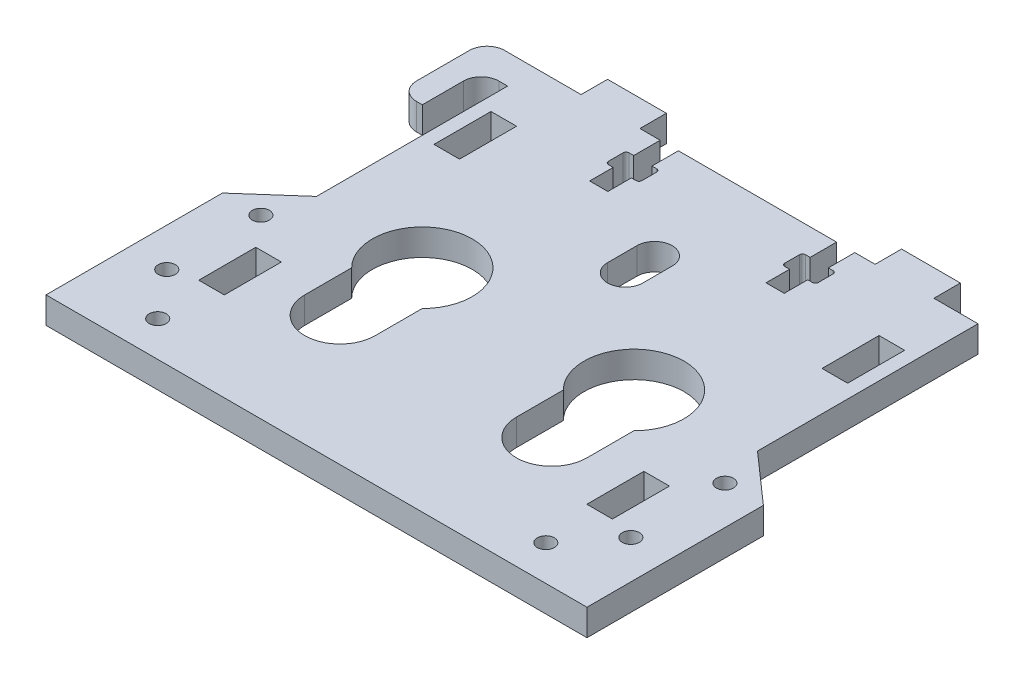
SolidWorks part; units mm, degrees
ref_plane "Front Plane" through (0, 0, 0) normal (0, 0, 1) x (1, 0, 0)
ref_plane "Top Plane" through (0, 0, 0) normal (0, 1, 0) x (1, 0, 0)
ref_plane "Right Plane" through (0, 0, 0) normal (1, 0, 0) x (0, 0, -1)
sketch "Sketch1" plane through (0, 0, 0) normal (0, 1, 0) x (1, 0, 0)
  line L1 (-37.5, 37.5) -> (37.5, 37.5)
  line L2 (-37.5, 37.5) -> (-37.5, -37.5)
  line L3 (-37.5, -37.5) -> (37.5, -37.5)
  line L4 (37.5, 37.5) -> (37.5, -37.5)
  line L5 (-37.5, 37.5) -> (37.5, -37.5) construction
  line L6 (-37.5, -37.5) -> (37.5, 37.5) construction
  point P0 (0, 0)
  dimension "D1" = 75
  dimension "D2" = 75
extrude "MainShape" add sketch "Sketch1" along normal blind 4.5
sketch "Sketch2" plane through (0, 4.5, 0) normal (0, 1, 0) x (1, 0, 0)
  line L0 (0, -37.5) -> (0, 37.5) construction
  line L1 (-37.5, -37.5) -> (37.5, -37.5) construction
  line L2 (37.5, 37.5) -> (-37.5, 37.5) construction
  line L4 (-5, 42) -> (5, 42)
  line L5 (-5, 42) -> (-5, 33)
  line L6 (-5, 33) -> (5, 33)
  line L7 (5, 42) -> (5, 33)
  line L8 (-5, 42) -> (5, 33) construction
  line L9 (-5, 33) -> (5, 42) construction
  dimension "D1" = 10
  dimension "D2" = 4.5
extrude "Tab1" [suppressed] add sketch "Sketch2" against normal through all
sketch "Sketch4" [suppressed] plane through (0, 4.5, 0) normal (0, 1, 0) x (1, 0, 0)
  line L0 (0, 42) -> (0, -37.5) construction
  line L1 (5, 42) -> (-5, 42) construction
  line L2 (-47.5, -37.5) -> (47.5, -37.5) construction
  line L3 (-40, 37.5) -> (-40, 27) construction
  line L4 (-5, 37.5) -> (-47.5, 37.5) construction
  line L5 (-38.25, 27) -> (-41.75, 27) construction
  line L6 (-41.75, 27) -> (-41.75, 37.5) construction
  line L7 (-38.25, 27) -> (-41.75, 27)
  line L8 (-41.75, 27) -> (-41.75, 29.5)
  line L9 (-41.75, 29.5) -> (-42.75, 29.5)
  line L10 (-43, 29.75) -> (-43, 33.45)
  line L11 (-42.75, 33.7) -> (-41.75, 33.7)
  line L12 (-41.75, 33.7) -> (-41.75, 37.5)
  line L13 (-41.75, 37.5) -> (-38.25, 37.5)
  line L14 (-38.25, 27) -> (-38.25, 37.5) construction
  line L15 (-38.25, 33.7) -> (-38.25, 37.5)
  line L16 (-37.25, 33.7) -> (-38.25, 33.7)
  line L17 (-37, 29.75) -> (-37, 33.45)
  line L18 (-38.25, 29.5) -> (-37.25, 29.5)
  line L19 (-38.25, 27) -> (-38.25, 29.5)
  line L20 (38.25, 27) -> (38.25, 37.5) construction
  line L21 (41.75, 27) -> (41.75, 37.5) construction
  line L22 (38.25, 27) -> (41.75, 27) construction
  line L23 (40, 37.5) -> (40, 27) construction
  line L24 (38.25, 27) -> (38.25, 29.5)
  line L25 (38.25, 29.5) -> (37.25, 29.5)
  line L26 (37, 29.75) -> (37, 33.45)
  line L27 (37.25, 33.7) -> (38.25, 33.7)
  line L28 (38.25, 33.7) -> (38.25, 37.5)
  line L29 (41.75, 37.5) -> (38.25, 37.5)
  line L30 (41.75, 33.7) -> (41.75, 37.5)
  line L31 (42.75, 33.7) -> (41.75, 33.7)
  line L32 (43, 29.75) -> (43, 33.45)
  line L33 (41.75, 29.5) -> (42.75, 29.5)
  line L34 (41.75, 27) -> (41.75, 29.5)
  line L35 (38.25, 27) -> (41.75, 27)
  arc A0 (-42.75, 29.5) -> (-43, 29.75) centre (-42.75, 29.75) cw
  arc A1 (-37, 29.75) -> (-37.25, 29.5) centre (-37.25, 29.75) cw
  arc A2 (-37.25, 33.7) -> (-37, 33.45) centre (-37.25, 33.45) cw
  arc A3 (-43, 33.45) -> (-42.75, 33.7) centre (-42.75, 33.45) cw
  arc A4 (43, 33.45) -> (42.75, 33.7) centre (42.75, 33.45) ccw
  arc A5 (37.25, 33.7) -> (37, 33.45) centre (37.25, 33.45) ccw
  arc A6 (37, 29.75) -> (37.25, 29.5) centre (37.25, 29.75) ccw
  arc A7 (42.75, 29.5) -> (43, 29.75) centre (42.75, 29.75) ccw
  point P24 (-43, 29.5)
  point P27 (-37, 29.5)
  point P30 (-37, 33.7)
  point P33 (-43, 33.7)
  point P56 (43, 33.7)
  point P57 (37, 33.7)
  point P58 (37, 29.5)
  point P59 (43, 29.5)
  dimension "D7" = 0.5
  dimension "D1" = 11
  dimension "D2" = 1.55
  dimension "D3" = 3.5
  dimension "D4" = 2.85
  dimension "D5" = 8
  dimension "D6" = 40
extrude "Cut-Extrude2" [suppressed] cut sketch "Sketch4" against normal through all
sketch "Sketch5" plane through (0, 4.5, 0) normal (0, 1, 0) x (1, 0, 0)
  line L0 (0, -37.5) -> (0, 37.5) construction
  line L1 (-37.5, -37.5) -> (37.5, -37.5) construction
  line L3 (33, 37.5) -> (33, -37.5) construction
  line L4 (37.5, 37.5) -> (-37.5, 37.5) construction
  line L5 (-33, 37.5) -> (-33, -37.5) construction
  line L6 (30.825, 27.35) -> (35.175, 27.35)
  line L7 (30.825, 27.35) -> (30.825, 17.65)
  line L8 (30.825, 17.65) -> (35.175, 17.65)
  line L9 (35.175, 27.35) -> (35.175, 17.65)
  line L10 (30.825, 27.35) -> (35.175, 17.65) construction
  line L11 (30.825, 17.65) -> (35.175, 27.35) construction
  line L12 (-30.825, 17.65) -> (-35.175, 27.35) construction
  line L13 (-30.825, 27.35) -> (-35.175, 17.65) construction
  line L14 (-35.175, 27.35) -> (-35.175, 17.65)
  line L15 (-30.825, 17.65) -> (-35.175, 17.65)
  line L16 (-30.825, 27.35) -> (-30.825, 17.65)
  line L17 (-30.825, 27.35) -> (-35.175, 27.35)
  line L18 (-37.5, 2.5) -> (37.5, 2.5) construction
  line L19 (-37.5, 37.5) -> (-37.5, -37.5) construction
  line L20 (37.5, -37.5) -> (37.5, 37.5) construction
  line L21 (-30.825, -22.35) -> (-35.175, -12.65) construction
  line L22 (-30.825, -12.65) -> (-35.175, -22.35) construction
  line L23 (30.825, -12.65) -> (35.175, -22.35) construction
  line L24 (30.825, -22.35) -> (35.175, -12.65) construction
  line L25 (-30.825, -22.35) -> (-35.175, -22.35)
  line L26 (-30.825, -22.35) -> (-30.825, -12.65)
  line L27 (-30.825, -12.65) -> (-35.175, -12.65)
  line L28 (-35.175, -22.35) -> (-35.175, -12.65)
  line L29 (35.175, -22.35) -> (35.175, -12.65)
  line L30 (30.825, -12.65) -> (35.175, -12.65)
  line L31 (30.825, -22.35) -> (30.825, -12.65)
  line L32 (30.825, -22.35) -> (35.175, -22.35)
  line L33 (-30.825, 27.35) -> (-35.175, 17.65) construction
  line L34 (-37.5, 37.5) -> (37.5, 37.5) construction
  line L35 (37.5, 37.5) -> (-37.5, 37.5) construction
  point P10 (33, 22.5)
  point P21 (-33, 22.5)
  point P36 (-33, -17.5)
  point P37 (33, -17.5)
  dimension "D1" = 33
  dimension "D2" = 9.7
  dimension "D3" = 4.35
  dimension "D4" = 15
  dimension "D5" = 40
extrude "Cut-Extrude3" cut sketch "Sketch5" against normal through all
sketch "Sketch6" plane through (0, 4.5, 0) normal (0, 1, 0) x (1, 0, 0)
  line L0 (-18, -37.5) -> (-18, 28) construction
  line L1 (-24, -15.5) -> (-24, -7.5208)
  line L3 (-37.5, -15.5) -> (37.5, -15.5) construction
  line L4 (-37.5, 37.5) -> (-37.5, -37.5) construction
  line L5 (37.5, -37.5) -> (37.5, 37.5) construction
  line L6 (37.5, 37.5) -> (-37.5, 37.5) construction
  line L7 (-37.5, -37.5) -> (37.5, -37.5) construction
  line L8 (-12, -15.5) -> (-12, -7.5208)
  line L9 (-37.5, 37.5) -> (37.5, 37.5) construction
  arc A0 (-24, -15.5) -> (-12, -15.5) centre (-18, -15.5) ccw
  arc A2 (-12, -7.5208) -> (-24, -7.5208) centre (-18, -1.5) ccw
  dimension "D1" = 12
  dimension "D6" = 8.5
  dimension "D2" = 53
  dimension "D3" = 0
  dimension "D5" = 0
  dimension "D7" = 14
  dimension "D4" = 18
extrude "Cut-Extrude4" cut sketch "Sketch6" against normal through all
sketch "Sketch13" plane through (0, 4.5, 0) normal (0, 1, 0) x (1, 0, 0)
  line L0 (-37.5, 0) -> (-46, -7.5)
  line L1 (-37.5, 37.5) -> (-37.5, -37.5) construction
  line L2 (-46, -7.5) -> (-46, -37.5)
  line L3 (-46, -37.5) -> (-37.5, -37.5)
  line L4 (-37.5, -37.5) -> (-37.5, 0)
  line L5 (0, 37.5) -> (0, -37.5) construction
  line L6 (37.5, 37.5) -> (-37.5, 37.5) construction
  line L7 (-37.5, -37.5) -> (37.5, -37.5) construction
  line L8 (37.5, -37.5) -> (37.5, 0)
  line L9 (46, -37.5) -> (37.5, -37.5)
  line L10 (46, -7.5) -> (46, -37.5)
  line L11 (37.5, 0) -> (46, -7.5)
  line L12 (-37.5, -37.5) -> (-37.5, 0)
  line M23 (37.5, -37.5) -> (37.5, 37.5)
  line M25 (-37.5, 37.5) -> (-37.5, -37.5)
  dimension "D1" = 46
  dimension "D2" = 30
extrude "Boss-Extrude2" add sketch "Sketch13" against normal through all contours L2 L3 L0 M25 | L11 L9 L10 M23 region at (-41.5926, 4.5, 20.5556) region at (41.5926, 4.5, 20.5556)
sketch "Sketch8" plane through (0, 4.5, 0) normal (0, 1, 0) x (1, 0, 0)
  line L0 (-18, -9.5) -> (-18, -21.5) construction
  line L1 (-18, -15.5) -> (-39.46, -15.5) construction
  line L2 (-39.46, -23.5) -> (-39.46, -7.5) construction
  line L3 (-18, -21.5) -> (-18, -9.5) construction
  circle A0 centre (-39.46, -7.5) radius 1.45
  circle A1 centre (-18, -15.5) radius 6 construction
  circle A2 centre (-39.46, -23.5) radius 1.45
  dimension "D3" = 2.9
  dimension "D1" = 0
  dimension "D2" = 8
  dimension "D4" = 21.46
extrude "Cut-Extrude6" cut sketch "Sketch8" against normal through all
mirror "Mirror1" about plane through (0, 0, 0) normal (1, 0, 0) of "Cut-Extrude6", "Cut-Extrude4"
sketch "Sketch11" plane through (0, 4.5, 0) normal (0, 1, 0) x (1, 0, 0)
  line L0 (0, 37.5) -> (0, -37.5) construction
  line L1 (37.5, 37.5) -> (-37.5, 37.5) construction
  line L2 (-46, -37.5) -> (46, -37.5) construction
  line L3 (-25, 42) -> (-25, 37.5) construction
  line L4 (-30, 37.5) -> (-20, 37.5)
  line L5 (-30, 37.5) -> (-30, 42)
  line L6 (-30, 42) -> (-20, 42)
  line L7 (-20, 37.5) -> (-20, 42)
  line L8 (25, 42) -> (25, 37.5) construction
  line L9 (20, 37.5) -> (20, 42)
  line L10 (30, 42) -> (20, 42)
  line L11 (30, 37.5) -> (30, 42)
  line L12 (30, 37.5) -> (20, 37.5)
  dimension "D1" = 10
  dimension "D2" = 4.5
  dimension "D3" = 25
extrude "RearTabs" add sketch "Sketch11" against normal through all
sketch "Sketch12" plane through (0, 4.5, 0) normal (0, 1, 0) x (1, 0, 0)
  line L0 (-15, 0) -> (-15, 37.5) construction
  line L1 (20, 37.5) -> (-20, 37.5) construction
  line L2 (-13.45, 37.5) -> (-16.55, 37.5)
  line L3 (-16.55, 37.5) -> (-16.55, 33)
  line L4 (-16.55, 33) -> (-17.35, 33)
  line L5 (-17.85, 32.5) -> (-17.85, 30)
  line L6 (-17.35, 29.5) -> (-16.55, 29.5)
  line L7 (-16.55, 29.5) -> (-16.55, 25.5)
  line L8 (-16.55, 25.5) -> (-13.45, 25.5)
  line L9 (-13.45, 29.5) -> (-13.45, 25.5)
  line L10 (-12.65, 29.5) -> (-13.45, 29.5)
  line L11 (-12.15, 32.5) -> (-12.15, 30)
  line L12 (-13.45, 33) -> (-12.65, 33)
  line L13 (-13.45, 37.5) -> (-13.45, 33)
  line L14 (0, 37.5) -> (0, 23.4067) construction
  line L15 (13.45, 37.5) -> (13.45, 33)
  line L16 (13.45, 33) -> (12.65, 33)
  line L17 (12.15, 32.5) -> (12.15, 30)
  line L18 (12.65, 29.5) -> (13.45, 29.5)
  line L19 (13.45, 29.5) -> (13.45, 25.5)
  line L20 (16.55, 25.5) -> (13.45, 25.5)
  line L21 (16.55, 29.5) -> (16.55, 25.5)
  line L22 (17.35, 29.5) -> (16.55, 29.5)
  line L23 (17.85, 32.5) -> (17.85, 30)
  line L24 (16.55, 33) -> (17.35, 33)
  line L25 (16.55, 37.5) -> (16.55, 33)
  line L26 (13.45, 37.5) -> (16.55, 37.5)
  arc A0 (-17.85, 30) -> (-17.35, 29.5) centre (-17.35, 30) ccw
  arc A1 (-17.35, 33) -> (-17.85, 32.5) centre (-17.35, 32.5) ccw
  arc A2 (-12.65, 33) -> (-12.15, 32.5) centre (-12.65, 32.5) cw
  arc A3 (-12.15, 30) -> (-12.65, 29.5) centre (-12.65, 30) cw
  arc A4 (12.15, 30) -> (12.65, 29.5) centre (12.65, 30) ccw
  arc A5 (12.65, 33) -> (12.15, 32.5) centre (12.65, 32.5) ccw
  arc A6 (17.35, 33) -> (17.85, 32.5) centre (17.35, 32.5) cw
  arc A7 (17.85, 30) -> (17.35, 29.5) centre (17.35, 30) cw
  point P14 (-17.85, 29.5)
  point P17 (-17.85, 33)
  point P25 (-15, 25.5)
  point P28 (-12.15, 33)
  point P29 (-12.15, 29.5)
  point P53 (12.15, 29.5)
  point P54 (12.15, 33)
  point P55 (15, 25.5)
  point P56 (17.85, 33)
  point P57 (17.85, 29.5)
  dimension "D5" = 8
  dimension "D1" = 12
  dimension "D6" = 0.5
  dimension "D2" = 3.5
  dimension "D3" = 2.85
  dimension "D4" = 1.55
  dimension "D7" = 15
extrude "FrontScrewSlot" cut sketch "Sketch12" against normal through all
sketch "Sketch14" plane through (0, 4.5, 0) normal (0, 1, 0) x (1, 0, 0)
  line L0 (-33, 27.35) -> (-33, -37.5) construction
  line L1 (-30.825, 27.35) -> (-35.175, 27.35) construction
  line L2 (-46, -37.5) -> (46, -37.5) construction
  line L3 (-30, 37.5) -> (-37.5, 37.5) construction
  line L4 (0, 0) -> (0, -37.5) construction
  line L5 (33, 27.35) -> (33, -37.5) construction
  line L6 (-33, 27.35) -> (-33, -37.5) construction
  circle A0 centre (-33, -31.5) radius 1.45
  circle A1 centre (33, -31.5) radius 1.45
  dimension "D2" = 2.9
  dimension "D1" = 69
extrude "BraceScrews" cut sketch "Sketch14" against normal through all
sketch "Sketch15" plane through (0, 4.5, 0) normal (0, 1, 0) x (1, 0, 0)
  line L0 (0, -37.5) -> (0, 25.5) construction
  line L1 (-46, -37.5) -> (46, -37.5) construction
  line L2 (-16.55, 25.5) -> (-13.45, 25.5) construction
  line L3 (16, 27.5) -> (-16, 27.5) construction
  line L4 (-16.55, 37.5) -> (-20, 37.5) construction
  line L5 (-18.175, 32.35) -> (-13.825, 32.35)
  line L6 (-18.175, 32.35) -> (-18.175, 22.65)
  line L7 (-18.175, 22.65) -> (-13.825, 22.65)
  line L8 (-13.825, 32.35) -> (-13.825, 22.65)
  line L9 (-18.175, 32.35) -> (-13.825, 22.65) construction
  line L10 (-18.175, 22.65) -> (-13.825, 32.35) construction
  line L11 (18.175, 22.65) -> (13.825, 32.35) construction
  line L12 (18.175, 32.35) -> (13.825, 22.65) construction
  line L13 (13.825, 32.35) -> (13.825, 22.65)
  line L14 (18.175, 22.65) -> (13.825, 22.65)
  line L15 (18.175, 32.35) -> (18.175, 22.65)
  line L16 (18.175, 32.35) -> (13.825, 32.35)
  point P19 (0, 27.5)
  dimension "D1" = 16
  dimension "D2" = 4.35
  dimension "D3" = 9.7
  dimension "D4" = 10
extrude "FanTabs" [suppressed] cut sketch "Sketch15" against normal through all
sketch "Sketch16" plane through (0, 4.5, 0) normal (0, 1, 0) x (1, 0, 0)
  line L0 (0, 0) -> (0, 37.5) construction
  line L2 (0, 20) -> (0, 15) construction
  line L3 (3, 20) -> (3, 15)
  line L4 (-3, 20) -> (-3, 15)
  line L5 (13.45, 37.5) -> (-13.45, 37.5) construction
  arc A0 (3, 20) -> (-3, 20) centre (0, 20) ccw
  arc A1 (-3, 15) -> (3, 15) centre (0, 15) ccw
  point P7 (0, 17.5)
  dimension "D1" = 3
  dimension "D2" = 20
  dimension "D3" = 5
extrude "WiringSlot" cut sketch "Sketch16" against normal through all
sketch "Sketch17" [suppressed] plane through (0, 4.5, 0) normal (0, 1, 0) x (1, 0, 0)
  line L0 (-37.5, 14.5) -> (-37.5, 10.5) construction
  line L3 (-37.5, 37.5) -> (-37.5, 0) construction
  line L4 (-36, 14.5) -> (-36, 10.5)
  line L5 (-39, 14.5) -> (-39, 10.5)
  line L6 (-37.5, 14.5) -> (-37.5, 10.5) construction
  line L7 (-34, 14.5) -> (-34, 10.5)
  line L8 (-41, 14.5) -> (-41, 10.5)
  line L9 (-41, 12.5) -> (-37.5, 12.5) construction
  line L10 (0, 0) -> (0, -12.1805) construction
  arc A0 (-36, 14.5) -> (-39, 14.5) centre (-37.5, 14.5) ccw
  arc A1 (-39, 10.5) -> (-36, 10.5) centre (-37.5, 10.5) ccw
  arc A2 (-34, 14.5) -> (-41, 14.5) centre (-37.5, 14.5) ccw
  arc A3 (-41, 10.5) -> (-34, 10.5) centre (-37.5, 10.5) ccw
  point P4 (-37.5, 12.5)
  point P10 (-37.5, 12.5)
  dimension "D4" = 4
  dimension "D5" = 25
  dimension "D1" = 0
  dimension "D2" = 2
  dimension "D3" = 1.5
extrude "Boss-Extrude3" [suppressed] add sketch "Sketch17" against normal through all
mirror "Mirror2" [suppressed] about plane through (0, 0, 0) normal (1, 0, 0)
sketch "Sketch18" [suppressed] plane through (0, 4.5, 0) normal (0, 1, 0) x (1, 0, 0)
  line L0 (0, -37.5) -> (0, 47.6111) construction
  line L1 (-45, -37.5) -> (45, -37.5) construction
  line L2 (-12, 2) -> (-12, -19.46) construction
  line L3 (-4, -19.46) -> (-20, -19.46) construction
  circle A0 centre (-12, 2) radius 5
  circle A1 centre (-20, -19.46) radius 1.45
  circle A2 centre (-4, -19.46) radius 1.45
  dimension "D2" = 8
  dimension "D4" = 21.46
  dimension "D1" = 2.9
  dimension "D3" = 10
  dimension "D5" = 12
  dimension "D6" = 2
extrude "Cut-Extrude7" [suppressed] cut sketch "Sketch18" against normal through all
mirror "Mirror3" [suppressed] about plane through (0, 0, 0) normal (1, 0, 0)
sketch "Sketch19" [suppressed] plane through (0, 4.5, 0) normal (0, 1, 0) x (1, 0, 0)
  line L0 (-17, 2) -> (-7, 2) construction
  line L1 (-12, 2) -> (-4, 2) construction
  line L2 (-12, 4) -> (-4, 4)
  line L3 (-12, 0) -> (-4, 0)
  line L4 (-12, 7) -> (-12, -3) construction
  line L5 (0, 0) -> (0, 6.8806) construction
  line L6 (12, 7) -> (12, -3) construction
  line L7 (17, 2) -> (7, 2) construction
  line L8 (12, 2) -> (4, 2) construction
  line L9 (12, 4) -> (4, 4)
  line L10 (12, 0) -> (4, 0)
  circle A0 centre (-12, 2) radius 5 construction
  arc A1 (-12, 4) -> (-12, 0) centre (-12, 2) ccw
  arc A2 (-4, 0) -> (-4, 4) centre (-4, 2) ccw
  arc A3 (12, 4) -> (12, 0) centre (12, 2) cw
  arc A4 (4, 0) -> (4, 4) centre (4, 2) cw
  point P6 (-8, 2)
  point P23 (8, 2)
  dimension "D1" = 2
  dimension "D2" = 8
extrude "Cut-Extrude8" [suppressed] cut sketch "Sketch19" against normal through all
sketch "Sketch20" plane through (0, 4.5, 0) normal (0, 1, 0) x (1, 0, 0)
  line L0 (0, 0) -> (0, -37.5) construction
  line L1 (-46, -37.5) -> (46, -37.5) construction
  line L2 (-26.9758, -32.9017) -> (-26.9758, -26.6196)
  line L3 (-26.9758, -26.6196) -> (-6.5592, -26.6196)
  line L4 (-6.5592, -26.6196) -> (-6.5592, 9.4097)
  line L5 (-6.5592, 9.4097) -> (6.5592, 9.4097)
  line L6 (-26.9758, -32.9017) -> (26.9758, -32.9017)
  line L7 (6.5592, -26.6196) -> (6.5592, 9.4097)
  line L8 (26.9758, -26.6196) -> (6.5592, -26.6196)
  line L9 (26.9758, -32.9017) -> (26.9758, -26.6196)
  point P12 (0, -32.9017)
  point P13 (0, 9.4097)
extrude "Cut-Extrude9" [suppressed] cut sketch "Sketch20" against normal through all
sketch "Sketch21" plane through (0, 4.5, 0) normal (0, 1, 0) x (1, 0, 0)
  line L0 (-46, -37.5) -> (-46, 37.5) construction
  line L1 (-37, 37.5) -> (-43, 37.5)
  line L4 (-46, 34.5) -> (-46, 25.5)
  line L5 (-43, 22.5) -> (-42, 22.5)
  line L6 (-42, 22.5) -> (-42, 29.5)
  line L7 (-39, 32.5) -> (-37, 32.5)
  line L9 (-37, 32.5) -> (-37, 37.5)
  line L10 (-30, 37.5) -> (-37.5, 37.5) construction
  line L11 (-37.5, 37.5) -> (-37.5, 0) construction
  arc A0 (-42, 29.5) -> (-39, 32.5) centre (-39, 29.5) cw
  arc A1 (-46, 25.5) -> (-43, 22.5) centre (-43, 25.5) ccw
  arc A2 (-43, 37.5) -> (-46, 34.5) centre (-43, 34.5) ccw
  point P19 (-46, 22.5)
  point P24 (-42, 37.5)
  dimension "D1" = 3
  dimension "D4" = 3
  dimension "D2" = 15
  dimension "D3" = 5
  dimension "D5" = 4
  dimension "D6" = 0.5
  dimension "D7" = 0
extrude "Boss-Extrude4" add sketch "Sketch21" against normal through all
sketch "Sketch22" plane through (0, 4.5, 0) normal (0, 1, 0) x (1, 0, 0)
  line L0 (-46, -7.5) -> (-46, 13.5)
  line L1 (-43, 16.5) -> (-42, 16.5)
  line L2 (-42, 16.5) -> (-42, -3.9706)
  line L3 (-37.5, 0) -> (-46, -7.5) construction
  line L4 (-42, -3.9706) -> (-46, -7.5)
  line L5 (-46, 16.5) -> (-46, 28.3122) construction
  line L6 (-46, 34.5) -> (-46, 25.5) construction
  line L7 (-42, 22.6875) -> (-42, 12.0504) construction
  line L8 (-42, 22.5) -> (-42, 29.5) construction
  arc A0 (-46, 13.5) -> (-43, 16.5) centre (-43, 13.5) cw
  dimension "D2" = 3
  dimension "D1" = 6
extrude "Boss-Extrude5" [suppressed] add sketch "Sketch22" against normal through all
mirror "Mirror6" [suppressed] about plane through (0, 0, 0) normal (1, 0, 0)
equation "\"X-ROD-SPACING\"=45"
equation "\"Y-ROD-SPACING\"=75"
equation "\"Z-ROD-SPACING\"=17.5"
equation "\"Y-BED-OFFSET\"=2"
equation "\"Y-BED-ROD-INSET\"=3.5"
equation "\"Y-BED-SCREW-SPACING\"=209"
equation "\"Y-BED-SCREW-CUTOUT-SLOT-HEIGHT\"=2"
equation "\"T-SLOT-NUT-FILLET-RADIUS\"=0.5"
equation "\"T-SLOT-SCREW-SHAFT-RADIUS\"=1.55"
equation "\"T-SLOT-SCREW-SHAFT-CUTOUT-LENGTH\"=11"
equation "\"T-SLOT-NUT-DEPTH\"=3.5"
equation "\"T-SLOT-NUT-WIDTH\"=2.85"
equation "\"T-SLOT-NUT-END-DISTANCE\"=8"
equation "\"ACRYLIC-THICKNESS\"=10"
equation "\"ACRYLIC-THICKNESS2\"=4.5"
equation "\"ACRYLIC-TAB-CUTOUT-SIZE\"=\"ACRYLIC-THICKNESS\"+\"ACRYLIC-TAB-TOLERANCE\"*2"
equation "\"ACRYLIC-TAB-WIDTH\"=\"ACRYLIC-THICKNESS\""
equation "\"ACRYLIC-M3-HOLE\"=2.9"
equation "\"SMOOTHROD-CAP-SCREW-DISTANCE\"=20"
equation "\"FRAME-WIDTH-INNER\"=370"
equation "\"NEMA17-HOLE-SPACING\"=31"
equation "\"NEMA17-CENTRAL-CUTOUT\"=22.5"
equation "\"Z-BRACKET-REACH\"=57"
equation "\"Z-ROD-INSET\"=13.5"
equation "\"TOP-BRACKET-SPACING\"=40"
equation "\"SMOOTHROD-X-LENGTH\"=350"
equation "\"SMOOTHROD-Y-LENGTH\"=350"
equation "\"SMOOTHROD-Z-LENGTH\"=350"
equation "\"SMOOTHROD-TIGHTENING-HEADROOM\"=.25"
equation "\"LEADSCREW-Z-LENGTH\"=300"
equation "\"SCREW-LENGTH-FRAME\"=\"ACRYLIC-THICKNESS\" + 10"
equation "\"SCREW-LENGTH-MOTOR\"=\"ACRYLIC-THICKNESS\" + 5"
equation "\"SCREW-LENGTH-EXTRUDER\"=28"
equation "\"SCREW-HEAD-RADIUS\"=6"
equation "\"PRINTED-X-SMOOTHROD-DIAMETER\"=8.8"
equation "\"PRINTED-X-SMOOTHROD-CUTOUT\"=10"
equation "\"PRINTED-X-BASE-HEIGHT\"=10"
equation "\"PRINTED-LM8UU-CUTOUT-SIZE\"=15.5"
equation "\"PRINTED-LM8UU-CUTOUT-LENGTH\"=24.5"
equation "\"PRINTED-X-IDLER-HEIGHT\"=16"
equation "\"PSU-MOUNTING-WIDTH\"=95"
equation "\"PSU-MOUNTING-HEIGHT\"=177"
equation "\"Y-BELT-TO-ROD-DISTANCE\"=20"
equation "\"SPOOL-HOLDER-ROD-SPACING\"=150"
equation "\"ACRYLIC-X-CARRIAGE-WIDTH\"=55"
equation "\"ACRYLIC-X-CARRIAGE-HEIGHT\"=75"
equation "\"ACRYLIC-X-CARRIAGE-SCREW-SPACING-X\"=15"
equation "\"ACRYLIC-X-CARRIAGE-SCREW-SPACING-Y\"=33"
equation "\"ACRYLIC-X-CARRIAGE-CENTER-TAB-SPACING\"=14"
equation "\"D1@MainShape\" = \"ACRYLIC-THICKNESS2\""
equation "\"D1@Sketch2\"=\"ACRYLIC-TAB-WIDTH\""
equation "\"D2@Sketch2\"=\"ACRYLIC-THICKNESS2\""
equation "\"D1@Sketch4\"=\"T-SLOT-SCREW-SHAFT-CUTOUT-LENGTH\""
equation "\"D2@Sketch4\"=\"T-SLOT-SCREW-SHAFT-RADIUS\""
equation "\"D3@Sketch4\"=\"T-SLOT-NUT-DEPTH\""
equation "\"D4@Sketch4\"=\"T-SLOT-NUT-WIDTH\""
equation "\"D5@Sketch4\"=\"T-SLOT-NUT-END-DISTANCE\""
equation "\"D7@Sketch4\"=\"T-SLOT-NUT-FILLET-RADIUS\""
equation "\"ACRYLIC-X-CARRIAGE-EXTRUDER-SHELF-DEPTH\"=\"ACRYLIC-X-CARRIAGE-EXTRUDER-OFFSET\" + 28"
equation "\"ACRYLIC-X-CARRIAGE-LM8UU-CUTOUT-WIDTH\"=24.25"
equation "\"ACRYLIC-X-CARRIAGE-EXTRUDER-BRACE-SPACING\"=23"
equation "\"ACRYLIC-X-CARRIAGE-EXTRUDER-BRACE-TAB-OFFSET\"=20"
equation "\"ACRYLIC-X-CARRIAGE-EXTRUDER-BRACE-HEIGHT\"=35"
equation "\"ACRYLIC-X-CARRIAGE-EXTRUDER-BRACE-SCREW-SPACING\"=22"
equation "\"D2@Sketch5\"=\"ACRYLIC-THICKNESS2-TAB-CUTOUT-HEIGHT\""
equation "\"D3@Sketch5\"=\"ACRYLIC-THICKNESS2-TAB-CUTOUT-WIDTH\""
equation "\"D3@Sketch8\"=\"ACRYLIC-M3-HOLE\""
equation "\"ACRYLIC-X-CARRIAGE-EXTRUDER-ANGLE\"=90"
equation "\"ACRYLIC-X-CARRIAGE-EXTRUDER-OFFSET\"=26"
equation "\"ACRYLIC-TAB-TOLERANCE\"=-.05"
equation "\"ACRYLIC-X-CARRIAGE-DUAL-WIDTH-MULTIPLIER\"=1.65"
equation "\"ACRYLIC-X-CARRIAGE-DUAL-HOTEND-SPACING\"=42"
equation "\"ACRYLIC-X-CARRIAGE-DUAL-WIDTH\"=75"
equation "\"ACRYLIC-X-CARRIAGE-DUAL-HOTEND-SEPARATION\"=36"
equation "\"ACRYLIC-X-CARRIAGE-DUAL-MOUNT-PLATE-DEPTH\"=75"
equation "\"ACRYLIC-X-CARRIAGE-DUAL-MOUNT-BRACE-WIDTH\"=33"
equation "\"D1@Sketch5\"=\"ACRYLIC-X-CARRIAGE-DUAL-MOUNT-BRACE-WIDTH\""
equation "\"ACRYLIC-X-CARRIAGE-DUAL-MOUNT-SCREW-WIDTH\"=40"
equation "\"D6@Sketch4\"=\"ACRYLIC-X-CARRIAGE-DUAL-MOUNT-SCREW-WIDTH\""
equation "\"D1@Sketch1\"=\"ACRYLIC-X-CARRIAGE-DUAL-WIDTH\""
equation "\"D2@Sketch1\"=\"ACRYLIC-X-CARRIAGE-DUAL-MOUNT-PLATE-DEPTH\""
equation "\"D4@Sketch6\"=\"ACRYLIC-X-CARRIAGE-DUAL-HOTEND-SEPARATION\"/2"
equation "\"D1@Sketch11\"=\"ACRYLIC-TAB-WIDTH\""
equation "\"D2@Sketch11\"=\"ACRYLIC-THICKNESS2\""
equation "\"D1@Sketch12\"=\"T-SLOT-SCREW-SHAFT-CUTOUT-LENGTH\"+1"
equation "\"D2@Sketch12\"=\"T-SLOT-NUT-DEPTH\""
equation "\"D3@Sketch12\"=\"T-SLOT-NUT-WIDTH\""
equation "\"D4@Sketch12\"=\"T-SLOT-SCREW-SHAFT-RADIUS\""
equation "\"D5@Sketch12\"=\"T-SLOT-NUT-END-DISTANCE\""
equation "\"D6@Sketch12\"=\"T-SLOT-NUT-FILLET-RADIUS\""
equation "\"D2@Sketch14\"=\"ACRYLIC-M3-HOLE\""
equation "\"D2@Sketch15\"=\"ACRYLIC-THICKNESS2-TAB-CUTOUT-WIDTH\""
equation "\"D3@Sketch15\"=\"ACRYLIC-THICKNESS2-TAB-CUTOUT-HEIGHT\""
equation "\"KERF\"=0.075"
equation "\"PRINTED-M3-HOLE\"=3.5"
equation "\"PRINTED-M3-NUT-AF\"=6.25"
equation "\"ACRYLIC-X-CARRIAGE-LM8UU-CUTOUT-HEIGHT\"=11.0"
equation "\"ACRYLIC-X-CARRIAGE-DUAL-FAN-OFFSET\"=52"
equation "\"ACRYLIC-X-CARRIAGE-DUAL-FAN-HEIGHT\"=20"
equation "\"BLOWER-FAN-WIDTH\"=15"
equation "\"ACRYLIC-THICKNESS-TAB-CUTOUT-WIDTH\"=\"ACRYLIC-THICKNESS\"-\"KERF\"*2"
equation "\"ACRYLIC-THICKNESS-TAB-CUTOUT-HEIGHT\"=\"ACRYLIC-TAB-WIDTH\"-\"KERF\"*4"
equation "\"ACRYLIC-THICKNESS2-TAB-CUTOUT-WIDTH\"=\"ACRYLIC-THICKNESS2\"-\"KERF\"*2"
equation "\"ACRYLIC-THICKNESS2-TAB-CUTOUT-HEIGHT\"=\"ACRYLIC-TAB-WIDTH\"-\"KERF\"*4"
equation "\"D1@Sketch18\"=\"ACRYLIC-M3-HOLE\""
equation "\"D7@Sketch12\"=\"ACRYLIC-X-CARRIAGE-SCREW-SPACING-X\""
